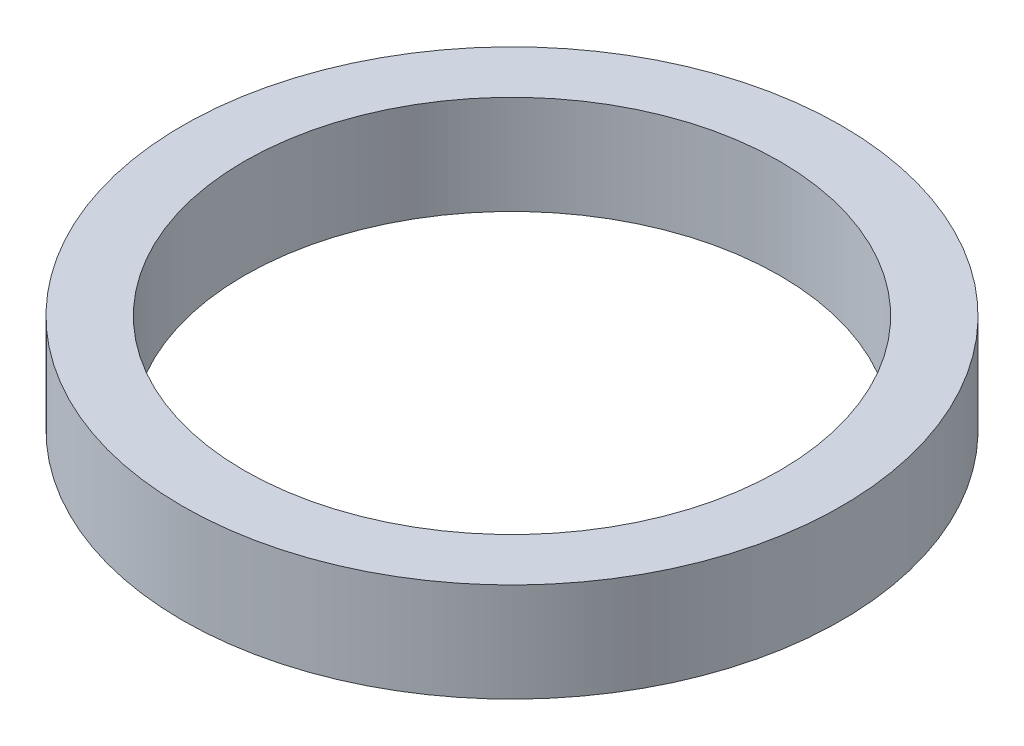
SolidWorks part; units mm, degrees
ref_plane "Front Plane" through (0, 0, 0) normal (0, 0, 1) x (1, 0, 0)
ref_plane "Top Plane" through (0, 0, 0) normal (0, 1, 0) x (1, 0, 0)
ref_plane "Right Plane" through (0, 0, 0) normal (1, 0, 0) x (0, 0, -1)
sketch "Sketch1" plane through (0, 0, 0) normal (0, 1, 0) x (1, 0, 0)
  circle A0 centre (0, 0) radius 40
  dimension "FLANGE_OD" = 80
extrude "Boss-Extrude1" add sketch "Sketch1" along normal blind 12
sketch "Sketch2" plane through (0, 0, 0) normal (0, 1, 0) x (1, 0, 0)
  circle A0 centre (0, 0) radius 32.5
  dimension "BORE_D" = 65
extrude "Cut-Extrude1" cut sketch "Sketch2" along normal through all
sketch "Sketch3" plane through (0, 12, 0) normal (0, 1, 0) x (1, 0, 0)
  circle A0 centre (0, 0) radius 17.9764 construction
  circle A1 centre (-17.9764, 0) radius 1.5
  dimension "BOLT_D" = 3
  dimension "BOLT_PCD" = 35.9528
extrude "Cut-Extrude2" cut sketch "Sketch3" against normal blind 10.384 rebuild error yes
pattern_circular "CirPattern1" count 6 over 360 rebuild error yes
